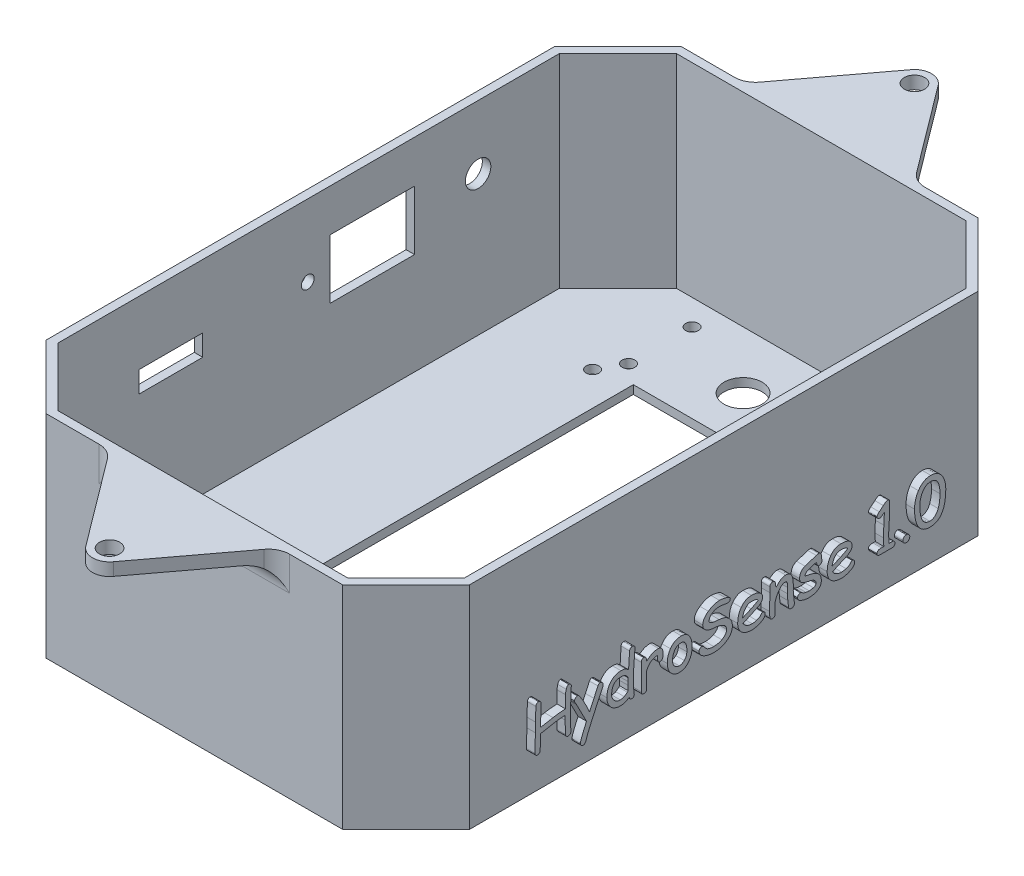
SolidWorks part; units mm, degrees
ref_plane "Front Plane" through (0, 0, 0) normal (0, 0, 1) x (1, 0, 0)
ref_plane "Top Plane" through (0, 0, 0) normal (0, 1, 0) x (1, 0, 0)
ref_plane "Right Plane" through (0, 0, 0) normal (1, 0, 0) x (0, 0, -1)
sketch "Sketch1" plane through (0, 0, 0) normal (0, 1, 0) x (1, 0, 0)
  line L0 (48, 146) -> (48, 0)
  line L1 (0, 0) -> (96, 0)
  line L2 (0, 0) -> (0, 146)
  line L3 (0, 146) -> (96, 146)
  line L4 (96, 0) -> (96, 146)
  line L6 (-2, -2) -> (98, -2)
  line L7 (-2, -2) -> (-2, 148)
  line L8 (-2, 148) -> (98, 148)
  line L9 (98, -2) -> (98, 148)
  line L10 (-2, -2) -> (98, 148) construction
  line L11 (-2, 148) -> (98, -2) construction
  point P7 (48, 73)
  dimension "D1" = 146
  dimension "D2" = 96
  dimension "D3" = 100
  dimension "D4" = 150
extrude "Boss-Extrude1" add sketch "Sketch1" along normal blind 2 contours L1 L4 L3 L0 | L3 L2 L1 L0 region at (72, 0, -73) region at (24, 0, -73)
extrude "Boss-Extrude2" add sketch "Sketch1<3>" along normal blind 50 contours L6 L9 L8 L7 L4 L1 L2 L3 region at (-0.1972, 0, -73)
sketch "Sketch1<3>" plane through (0, 0, 0) normal (0, 1, 0) x (1, 0, 0) same geometry as "Sketch1"
sketch "Sketch5" plane through (-2, 0, 0) normal (-1, 0, 0) x (0, 0, 1)
  line L0 (-148, 50) -> (-148, 0) construction
  line L1 (2, 50) -> (-148, 50) construction
  circle A0 centre (-113, 35) radius 3
  dimension "D1" = 6
  dimension "D2" = 35
  dimension "D3" = 15
extrude "Cut-Extrude1" cut sketch "Sketch5" against normal blind 70
sketch "Sketch6" plane through (0, 0, 0) normal (0, -1, 0) x (1, 0, 0)
  line L0 (48, 2) -> (48, -23.95)
  line L1 (-2, 2) -> (98, 2) construction
  line L2 (-2, -148) -> (98, -148) construction
  line L3 (48, -122.05) -> (48, -148)
  line L4 (17.965, -23.95) -> (78.035, -23.95)
  line L5 (17.965, -23.95) -> (17.965, -122.05)
  line L6 (17.965, -122.05) -> (78.035, -122.05)
  line L7 (78.035, -23.95) -> (78.035, -122.05)
  line L8 (48, -23.95) -> (48, -122.05)
  line L9 (78.035, -73) -> (17.965, -73)
  line L11 (28.42, -24.775) -> (67.58, -24.775)
  line L12 (28.42, -24.775) -> (28.42, -121.225)
  line L13 (28.42, -121.225) -> (67.58, -121.225)
  line L14 (67.58, -24.775) -> (67.58, -121.225)
  line L15 (28.42, -24.775) -> (67.58, -121.225) construction
  line L16 (28.42, -121.225) -> (67.58, -24.775) construction
  circle A0 centre (75.495, -26.49) radius 1.5
  circle A1 centre (20.505, -26.49) radius 1.5
  circle A2 centre (20.505, -119.51) radius 1.5
  circle A3 centre (75.495, -119.51) radius 1.5
  point P6 (48, -73)
  point P23 (48, -73)
  dimension "D3" = 3
  dimension "D1" = 98.1
  dimension "D2" = 60.07
  dimension "D4" = 2.54
  dimension "D5" = 2.54
  dimension "D6" = 96.45
  dimension "D7" = 39.16
extrude "Cut-Extrude2" cut sketch "Sketch6" against normal blind 70 contours A0 | L11 L12 L9 L8 | L14 L11 L8 L9 | L14 L9 L8 L13 | L12 L13 L8 L9 | A1 | A3 | A2 region at (57.79, 0, -48.8875) region at (38.21, 0, -48.8875) region at (38.21, 0, -97.1125) region at (57.79, 0, -97.1125) region at (75.495, 0, -26.49)
sketch "Sketch7" plane through (0, 0, 0) normal (0, -1, 0) x (1, 0, 0)
  line L0 (48, 2) -> (48, -24.775)
  line L1 (-2, 2) -> (98, 2) construction
  line L2 (28.42, -24.775) -> (67.58, -24.775) construction
  line L3 (32, -19.373) -> (64, -19.373)
  line L4 (64, -19.373) -> (64, -6.373)
  line L5 (64, -6.373) -> (32, -6.373)
  line L6 (32, -19.373) -> (32, -6.373)
  circle A0 centre (55, -12.873) radius 6
  circle A1 centre (45.05, -12.873) radius 1.5
  point P11 (48, -19.373)
  point P12 (48, -6.373)
  dimension "D3" = 12
  dimension "D4" = 3
  dimension "D1" = 16
  dimension "D2" = 13
  dimension "D5" = 9
  dimension "D6" = 9.95
extrude "Cut-Extrude3" cut sketch "Sketch7" against normal blind 70 contours A0 | A1 region at (55, 0, -12.873) region at (45.05, 0, -12.873)
sketch "Sketch8" plane through (0, 0, 0) normal (0, -1, 0) x (1, 0, 0)
  line L0 (98, 2) -> (98, -148) construction
  line L3 (38, -125.9424) -> (73, -125.9424)
  line L4 (73, -125.9424) -> (73, -138.9424)
  line L5 (73, -138.9424) -> (38, -138.9424)
  line L6 (38, -125.9424) -> (38, -138.9424)
  line L7 (73, -132.4424) -> (38, -132.4424)
  line L8 (43.1, -132.4424) -> (23.56, -132.4424)
  circle A1 centre (66.5, -132.4424) radius 4.5
  circle A2 centre (54.8, -132.4424) radius 4.5
  circle A3 centre (43.1, -132.4424) radius 4.5
  circle A4 centre (23.56, -124.9424) radius 1.5
  circle A5 centre (23.56, -139.9424) radius 1.5
  point P13 (55.5, -138.9424)
  point P14 (55.5, -125.9424)
  dimension "D1" = 6.5
  dimension "D5" = 9
  dimension "D6" = 9
  dimension "D8" = 9
  dimension "D11" = 3
  dimension "D2" = 25
  dimension "D3" = 13
  dimension "D4" = 6.5
  dimension "D7" = 11.7
  dimension "D9" = 11.7
  dimension "D10" = 19.54
  dimension "D12" = 7.5
extrude "Cut-Extrude4" cut sketch "Sketch8" against normal blind 70 contours A4 | A5 | A3 | A1 | A2
sketch "Sketch9" plane through (-2, 0, 0) normal (-1, 0, 0) x (0, 0, 1)
  line L0 (2, 50) -> (-148, 50) construction
  line L1 (-88, 26) -> (-88, 20.78)
  line L2 (-98, 40) -> (-78, 40)
  line L3 (-98, 40) -> (-98, 26)
  line L4 (-98, 26) -> (-78, 26)
  line L5 (-78, 40) -> (-78, 26)
  line L6 (-78, 33) -> (-72.78, 33)
  line L7 (-148, 50) -> (-148, 0) construction
  circle A0 centre (-88, 20.78) radius 1.5
  circle A1 centre (-72.78, 33) radius 1.5
  dimension "D5" = 3
  dimension "D7" = 3
  dimension "D1" = 10
  dimension "D2" = 14
  dimension "D3" = 20
  dimension "D4" = 5.22
  dimension "D6" = 5.22
  dimension "D8" = 50
extrude "Cut-Extrude5" cut sketch "Sketch9" against normal blind 70 contours L5 L2 L3 L4 | A1 region at (-2, 33, -88)
sketch "Sketch10" plane through (0, 50, 0) normal (0, 1, 0) x (1, 0, 0)
  line L0 (48, 148) -> (48, 168)
  line L1 (-2, 148) -> (98, 148) construction
  line L2 (28, 148) -> (68, 148)
  line L3 (68, 148) -> (51.2412, 170.3441)
  line L4 (28, 148) -> (44.7588, 170.3441)
  line L5 (98, 73) -> (-2, 73)
  line L6 (98, -2) -> (98, 148) construction
  line L7 (-2, -2) -> (-2, 148) construction
  line L8 (68, -2) -> (51.2412, -24.3441)
  line L9 (28, -2) -> (44.7588, -24.3441)
  line L10 (28, -2) -> (68, -2)
  circle A0 centre (48, 168) radius 2.4
  circle A1 centre (48, 168) radius 4
  circle A2 centre (48, -22) radius 2.4
  circle A3 centre (48, -22) radius 4
  line M13 (-2, -2) -> (98, -2)
  line M15 (98, 148) -> (-2, 148)
  dimension "D2" = 4.8
  dimension "D3" = 8
  dimension "D1" = 20
  dimension "D4" = 20
extrude "Boss-Extrude4" add sketch "Sketch10" against normal blind 3 contours A3 L9 L8 A2 | L9 A3 L8 M13 | A1 L0 L3 M15 | A1 L4 L0 M15 | A1 L3 L4 A0 region at (40.7303, 50, -155.5016) region at (55.2697, 50, -155.5016) region at (44.5387, 50, -166.2316) region at (48, 50, 9.5016) region at (48, 50, 25.8869)
fillet "Fillet2" radius 5 6 edges at (68, 48.5, 2) (48, 47, 2) (28, 48.5, 2) (28, 48.5, -148) (48, 47, -148) (68, 48.5, -148)
sketch "Sketch11" plane through (-2, 0, 0) normal (-1, 0, 0) x (0, 0, 1)
  line L0 (-48, 35) -> (-33, 35)
  line L2 (2, 50) -> (2, 0) construction
  line L3 (-33, 35) -> (-33, 30)
  line L4 (-33, 30) -> (-48, 30)
  line L5 (-48, 30) -> (-48, 35)
  line L6 (2, 50) -> (-148, 50) construction
  dimension "D1" = 35
  dimension "D2" = 5
  dimension "D3" = 15
  dimension "D4" = 20
sketch "Sketch12" plane through (98, 0, 0) normal (1, 0, 0) x (0, 0, -1)
  text T0 "HydroSense 1.0" font "Comic Sans MS" height 10
extrude "Boss-Extrude5" add sketch "Sketch12" along normal blind 2
sketch "Sketch13" plane through (0, 50, 0) normal (0, 1, 0) x (1, 0, 0)
  line L0 (-2, 73) -> (98, 73)
  line L1 (-2, -2) -> (-2, 148) construction
  line L2 (98, -2) -> (98, 148) construction
  line L3 (98, 148) -> (83, 148)
  line L4 (70.4999, 148) -> (98, 148) construction
  line L5 (98, 148) -> (98, 133)
  line L6 (83, 148) -> (98, 133)
  line L7 (-2, 148) -> (13, 148)
  line L8 (-2, 148) -> (25.5001, 148) construction
  line L9 (-2, 148) -> (-2, 133)
  line L10 (-2, 133) -> (13, 148)
  line L11 (-2, -2) -> (-2, 13)
  line L12 (-2, -2) -> (13, -2)
  line L13 (83, -2) -> (98, 13)
  line L14 (98, -2) -> (98, 13)
  line L15 (98, -2) -> (83, -2)
  line L16 (-2, 13) -> (13, -2)
  line L17 (5.5, 140.5) -> (6.9142, 139.0858)
  line L18 (6.9142, 139.0858) -> (-2, 130.1716)
  line L19 (6.9142, 139.0858) -> (15.8284, 148)
  line L20 (13, 148) -> (15.8284, 148)
  line L21 (-2, 130.1716) -> (-2, 133)
  line L22 (90.5, 140.5) -> (89.0858, 139.0858)
  line L23 (89.0858, 139.0858) -> (80.1716, 148)
  line L24 (80.1716, 148) -> (83, 148)
  line L25 (89.0858, 139.0858) -> (98, 130.1716)
  line L26 (98, 130.1716) -> (98, 133)
  line L27 (89.0858, 6.9142) -> (98, 15.8284)
  line L28 (80.1716, -2) -> (83, -2)
  line L29 (89.0858, 6.9142) -> (80.1716, -2)
  line L30 (90.5, 5.5) -> (89.0858, 6.9142)
  line L31 (-2, 15.8284) -> (-2, 13)
  line L32 (13, -2) -> (15.8284, -2)
  line L33 (6.9142, 6.9142) -> (15.8284, -2)
  line L34 (6.9142, 6.9142) -> (-2, 15.8284)
  line L35 (5.5, 5.5) -> (6.9142, 6.9142)
  line L36 (-2, 13) -> (13, -2)
  line L37 (-2, -2) -> (-2, 13)
  line L38 (-2, -2) -> (13, -2)
  line L39 (83, -2) -> (98, 13)
  line L40 (98, -2) -> (98, 13)
  line L41 (98, -2) -> (83, -2)
  line L42 (98, 15.8284) -> (98, 13)
  line L43 (-2, 13) -> (-2, 15.8284)
  line L44 (13, -2) -> (15.8284, -2)
  line L45 (80.1716, -2) -> (83, -2)
  line L46 (98, 15.8284) -> (98, 13)
  line M8 (96, 146) -> (96, 0)
  line M9 (96, 0) -> (0, 0)
  line M10 (0, 0) -> (0, 146)
  line M11 (0, 146) -> (96, 146)
  line M12 (-2, -2) -> (25.5001, -2)
  line M18 (70.4999, -2) -> (98, -2)
  line M19 (98, -2) -> (98, 148)
  line M20 (98, 148) -> (70.4999, 148)
  line M26 (25.5001, 148) -> (-2, 148)
  line M27 (-2, 148) -> (-2, -2)
  dimension "D1" = 15
  dimension "D2" = 15
  dimension "D3" = 15
  dimension "D4" = 15
  dimension "D5" = 2
  dimension "D6" = 2
extrude "Cut-Extrude7" cut sketch "Sketch13" against normal through all contours L13 M18 M19 M8 M9 | L13 M9 M8 | L16 M10 M9 | L16 M27 M12 M9 M10 | L10 M27 M10 M11 M26 | L10 M10 M11 | L6 M11 M8 | L6 M20 M11 M8 M19 region at (-1.7879, 50, -140.5) region at (-1.15, 50, -11.85) region at (3.6667, 50, -3.6667) region at (3.6667, 50, -142.3333) region at (96.2121, 50, -140.5) region at (92.3333, 50, -142.3333) region at (92.3333, 50, -3.6667) region at (97.15, 50, -11.85)
extrude "Boss-Extrude7" add sketch "Sketch13<3>" against normal blind 50 contours L17 L19 L10 M11 | L18 L17 L10 M10 | L23 L22 L6 M11 | L22 L25 L6 M8 | L16 L35 L34 M10 | L35 L16 L33 M9 | L30 L13 L27 M8 | L29 L13 M9 M18 | L13 L30 L29 M9 | L27 L13 M8 M19 | L33 L16 M9 M12 | L34 L16 M10 M27 | L18 L10 M10 M27 | L19 L10 M11 M26 | L23 L6 M11 M20 | L25 L6 M8 M19 region at (-1, 50, -132.5858) region at (-1, 50, -13.4142) region at (3.117, 50, -9.3509) region at (3.117, 50, -136.6491) region at (97, 50, -132.5858) region at (92.883, 50, -136.6491) region at (92.883, 50, -9.3509) region at (97, 50, -13.4142) region at (9.3509, 50, -3.117) region at (9.3509, 50, -142.883) region at (86.6491, 50, -142.883) region at (86.6491, 50, -3.117) region at (13.4142, 50, 1) region at (13.4142, 50, -147) region at (82.5858, 50, -147) region at (82.5858, 50, 1)
sketch "Sketch13<3>" plane through (0, 50, 0) normal (0, 1, 0) x (1, 0, 0) same geometry as "Sketch13"
extrude "Cut-Extrude8" cut sketch "Sketch11" against normal blind 70
